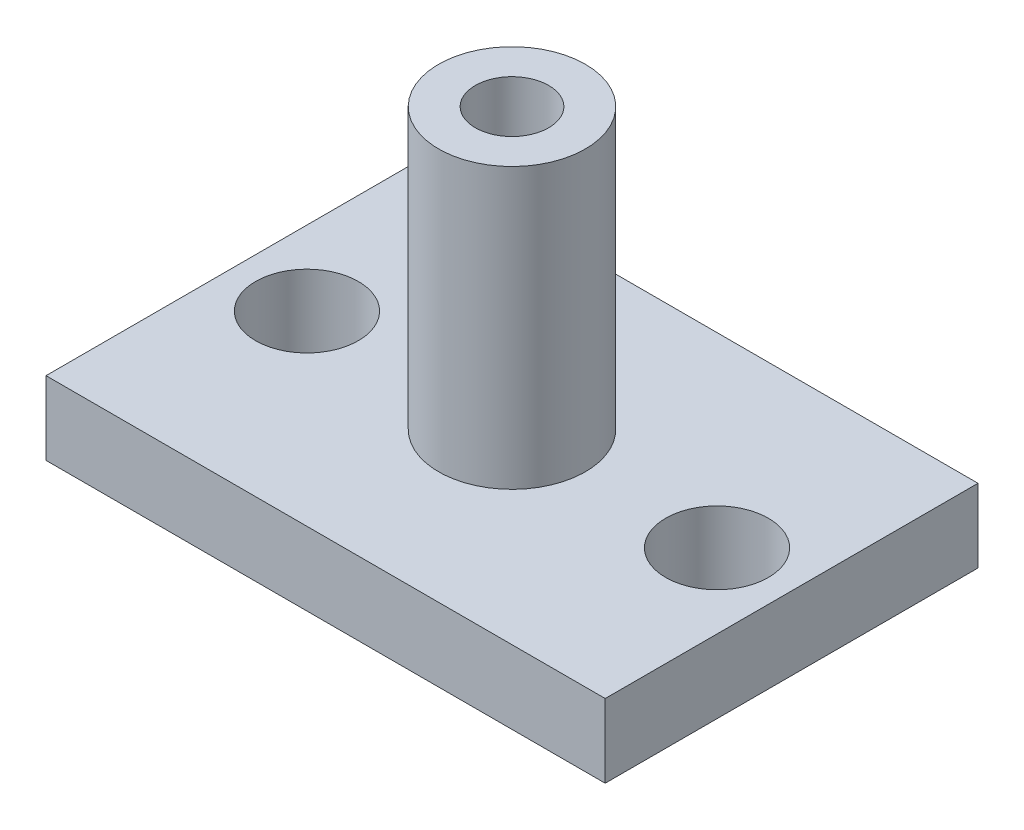
SolidWorks part; units mm, degrees
ref_plane "前视" through (0, 0, 0) normal (0, 0, 1) x (1, 0, 0)
ref_plane "上视" through (0, 0, 0) normal (0, 1, 0) x (1, 0, 0)
ref_plane "右视" through (0, 0, 0) normal (1, 0, 0) x (0, 0, -1)
sketch "Sketch1" plane through (0, 0, 0) normal (0, 1, 0) x (1, 0, 0)
  line L1 (-25.8417, 12.7) -> (12.2583, 12.7)
  line L2 (-25.8417, 12.7) -> (-25.8417, -12.7)
  line L3 (-25.8417, -12.7) -> (12.2583, -12.7)
  line L4 (12.2583, 12.7) -> (12.2583, -12.7)
  dimension "D1" = 25.4
  dimension "D2" = 38.1
extrude "Boss-Extrude1" add sketch "Sketch1" along normal blind 5
ref_point "Point1"
sketch "Sketch3" plane through (0, 5, 0) normal (0, 1, 0) x (1, 0, 0)
  circle A0 centre (-6.7917, 0) radius 5
  circle A1 centre (-6.7917, 0) radius 2.5
extrude "Boss-Extrude2" add sketch "Sketch3" along normal blind 19.05
ref_axis "Axis1" through (12.2583, 5, 0) along (-1, 0, 0)
sketch "Sketch4" plane through (0, 5, 0) normal (0, 1, 0) x (1, 0, 0)
  line L0 (12.2583, -12.7) -> (12.2583, 12.7) construction
  line L1 (-25.8417, 12.7) -> (-25.8417, -12.7) construction
  circle A0 centre (7.1783, 0) radius 3.5
  circle A1 centre (-20.7617, 0) radius 3.5
  point P0 (7.1783, 0)
  point P1 (12.2583, 0)
  point P4 (-20.7617, 0)
  dimension "D3" = 7
  dimension "D4" = 7
  dimension "D1" = 5.08
  dimension "D2" = 5.08
extrude "Cut-Extrude1" cut sketch "Sketch4" against normal through all
